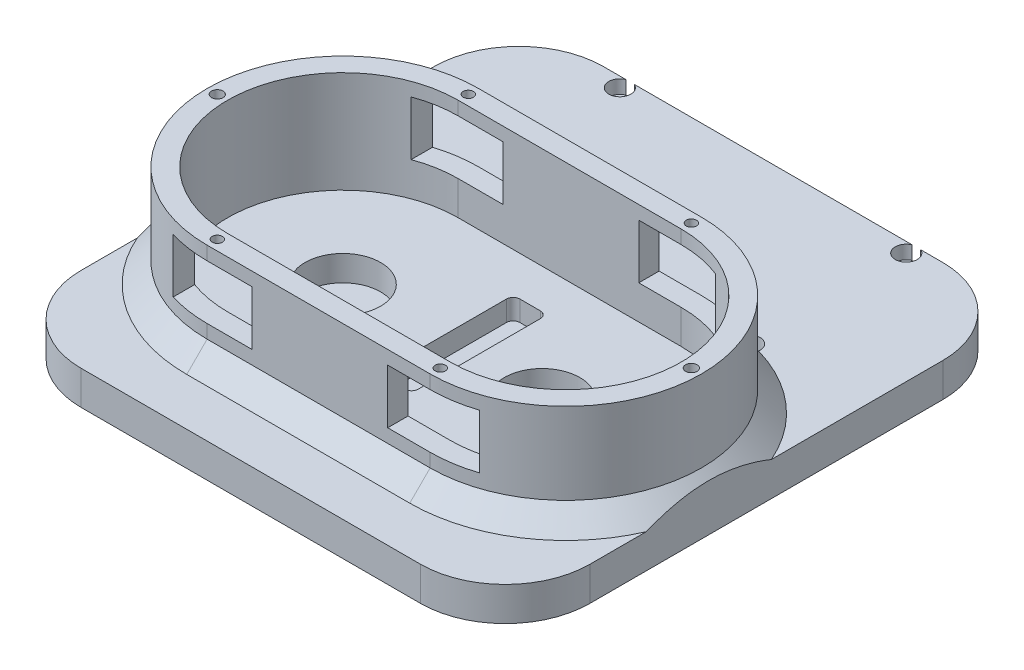
SolidWorks part; units mm, degrees
ref_plane "Front Plane" through (0, 0, 0) normal (0, 0, 1) x (1, 0, 0)
ref_plane "Top Plane" through (0, 0, 0) normal (0, 1, 0) x (1, 0, 0)
ref_plane "Right Plane" through (0, 0, 0) normal (1, 0, 0) x (0, 0, -1)
sketch "Sketch1" plane through (0, 0, 0) normal (0, 1, 0) x (1, 0, 0)
  line L0 (45, 40) -> (45, -40) construction
  line L8 (45, 40) -> (-20.73, 40)
  line L9 (45, -40) -> (-20.73, -40)
  arc A0 (45, -40) -> (45, 40) centre (45, 0) ccw
  circle A2 centre (38, 0) radius 28.73 construction
  arc A3 (-20.73, 40) -> (-20.73, -40) centre (-20.73, 0) ccw
  circle A4 centre (-20.73, 0) radius 30 construction
  point P0 (0, 0)
  dimension "D3" = 80
  dimension "D1" = 10
  dimension "D2" = 60
  dimension "D5" = 7
  dimension "D6" = 58.73
  dimension "D4" = 45
extrude "Boss-Extrude1" add sketch "Sketch1" along normal blind 10
sketch "Sketch2" plane through (0, 0, 0) normal (0, 1, 0) x (1, 0, 0)
  line L2 (-20.73, -40) -> (45, -40) construction
  line L3 (45, 40) -> (-20.73, 40) construction
  line L4 (45, 34) -> (-20.73, 34)
  line L5 (-20.73, -34) -> (45, -34)
  line L6 (45, 34) -> (-20.73, 34)
  line L7 (-20.73, -34) -> (45, -34)
  line L8 (-20.73, -40) -> (45, -40)
  line L9 (45, 40) -> (-20.73, 40)
  arc A2 (-20.73, 40) -> (-20.73, -40) centre (-20.73, 0) ccw construction
  arc A3 (45, -40) -> (45, 40) centre (45, 0) ccw construction
  arc A4 (45, -34) -> (45, 34) centre (45, 0) ccw
  arc A5 (-20.73, 34) -> (-20.73, -34) centre (-20.73, 0) ccw
  arc A6 (45, -34) -> (45, 34) centre (45, 0) ccw
  arc A7 (-20.73, 34) -> (-20.73, -34) centre (-20.73, 0) ccw
  arc A8 (-20.73, 40) -> (-20.73, -40) centre (-20.73, 0) ccw
  arc A9 (45, -40) -> (45, 40) centre (45, 0) ccw
  dimension "D1" = 6
extrude "Boss-Extrude2" add sketch "Sketch2" along normal blind 30 from surface starting at face at (12.135, 10, 0)
sketch "Sketch8" plane through (0, 0, 0) normal (0, 1, 0) x (1, 0, 0)
  line L0 (12.135, 40) -> (12.135, -40) construction
  line L1 (-20.73, 40) -> (45, 40) construction
  line L2 (45, -40) -> (-20.73, -40) construction
  line L3 (85, 0) -> (-60.73, 0) construction
  line L4 (-20.73, -40) -> (45, -40) construction
  line L5 (-62.865, -60) -> (87.135, -60)
  line L6 (-62.865, -60) -> (-62.865, 94)
  line L7 (-62.865, 94) -> (87.135, 94)
  line L8 (87.135, -60) -> (87.135, 94)
  arc A0 (45, -40) -> (45, 40) centre (45, 0) ccw construction
  arc A1 (-20.73, 40) -> (-20.73, -40) centre (-20.73, 0) ccw construction
  point P14 (12.135, 0)
  point P22 (12.135, 94)
  dimension "D1" = 54
  dimension "D2" = 150
  dimension "D3" = 20
extrude "Boss-Extrude3" add sketch "Sketch8" along normal blind 10
sketch "Sketch5" plane through (0, 0, 0) normal (0, 1, 0) x (1, 0, 0)
  arc A0 (-20.73, 40) -> (-20.73, -40) centre (-20.73, 0) ccw construction
  arc A1 (-20.73, 40) -> (-20.73, -40) centre (-20.73, 0) ccw construction
  arc A2 (45, -40) -> (45, 40) centre (45, 0) ccw construction
  arc A3 (45, -40) -> (45, 40) centre (45, 0) ccw construction
  circle A4 centre (-20.73, 0) radius 11.15
  circle A6 centre (38, 0) radius 11.15
  dimension "D1" = 7
  dimension "D2" = 22.3
extrude "Cut-Extrude2" cut sketch "Sketch5" against normal blind 7.5 from surface starting at face at (12.135, 10, 0)
sketch "Sketch7" plane through (0, 0, 0) normal (0, 0, 1) x (1, 0, 0)
  line L0 (45, 40) -> (45, 10) construction
  line L1 (-32.5, 20) -> (-7.5, 20)
  line L2 (-32.5, 20) -> (-32.5, 36)
  line L3 (-32.5, 36) -> (-7.5, 36)
  line L4 (-7.5, 20) -> (-7.5, 36)
  line L5 (-32.5, 20) -> (-7.5, 36) construction
  line L6 (-32.5, 36) -> (-7.5, 20) construction
  line L7 (32.5, 20) -> (57.5, 20)
  line L8 (32.5, 20) -> (32.5, 36)
  line L9 (32.5, 36) -> (57.5, 36)
  line L10 (57.5, 20) -> (57.5, 36)
  line L11 (32.5, 20) -> (57.5, 36) construction
  line L12 (32.5, 36) -> (57.5, 20) construction
  line L14 (-20, 44) -> (-20, 0) construction
  point P0 (-20, 28)
  point P5 (45, 28)
  dimension "D1" = 16
  dimension "D2" = 20
  dimension "D3" = 25
  dimension "D4" = 25
  dimension "D5" = 20
extrude "Cut-Extrude4" cut sketch "Sketch7" against normal through all both and the other way through all
chamfer "Chamfer1" distance 6 angle 45 4 edges at (12.135, 10, -40) (85, 10, 0) (-60.73, 10, 0) (12.135, 10, 40)
fillet "Fillet1" radius 25 4 edges at (-62.865, 5, -94) (-62.865, 5, 60) (87.135, 5, -94) (87.135, 5, 60)
sketch "Sketch9" plane through (0, 0, 0) normal (0, 1, 0) x (1, 0, 0)
  line L0 (79, 0) -> (85, 0) construction
  line L1 (-60.73, 0) -> (-54.73, 0) construction
  circle A0 centre (45, -37) radius 1.5
  circle A1 centre (-20.73, -37) radius 1.5
  circle A2 centre (45, 37) radius 1.5
  circle A3 centre (-20.73, 37) radius 1.5
  circle A4 centre (-57.73, 0) radius 1.7
  circle A5 centre (82, 0) radius 1.7
  arc A6 (45, -34) -> (45, 34) centre (45, 0) ccw construction
  arc A7 (45, -40) -> (45, 40) centre (45, 0) ccw construction
  arc A8 (-20.73, 40) -> (-20.73, -40) centre (-20.73, 0) ccw construction
  arc A9 (-20.73, 34) -> (-20.73, -34) centre (-20.73, 0) ccw construction
  dimension "D1" = 3
  dimension "D2" = 3.4
extrude "Cut-Extrude5" cut sketch "Sketch9" against normal up to surface (-36 mm away) from surface up to face at (45.032, 36, 36.4505) starting at face at (12.135, 40, 0)
sketch "Sketch10" plane through (-45.015, 10, -51.2) normal (0, 1, 0) x (1, 0, 0)
  line L0 (57.15, -11.2) -> (57.15, 55.5219) construction
  line L1 (24.285, -11.2) -> (90.015, -11.2) construction
  line L2 (107.15, 42.8) -> (7.15, 42.8) construction
  circle A4 centre (14.94, -6.52) radius 1.45
  circle A5 centre (99.36, -6.52) radius 1.45
  circle A6 centre (99.36, 39.8) radius 1.45
  circle A7 centre (14.94, 39.8) radius 1.45
  dimension "D1" = 2.9
  dimension "D3" = 46.32
  dimension "D2" = 84.42
  dimension "D4" = 3
extrude "Cut-Extrude6" cut sketch "Sketch10" against normal through all both and the other way through all
sketch "Sketch11" plane through (0, 0, 0) normal (0, 1, 0) x (1, 0, 0)
  circle A0 centre (-30.075, 44.68) radius 3.25
  circle A1 centre (-30.075, 91) radius 3.25
  circle A2 centre (54.345, 91) radius 3.25
  circle A3 centre (54.345, 44.68) radius 3.25
  dimension "D1" = 6.5
extrude "Cut-Extrude7" cut sketch "Sketch11" against normal blind 4 and the other way through all from surface starting at face at (-30.075, 10, -92.45)
sketch "Sketch12" plane through (0, 0, 0) normal (0, 1, 0) x (1, 0, 0)
  line L0 (15.135, 22.3477) -> (9.135, 22.3477) construction
  line L1 (15.135, 22.3477) -> (9.135, 22.3477)
  line L2 (17.135, -15.6523) -> (17.135, 20.3477) construction
  line L3 (17.135, -15.6523) -> (17.135, 20.3477)
  line L4 (7.135, 20.3477) -> (7.135, -15.6523)
  line L5 (9.135, -17.6523) -> (15.135, -17.6523)
  arc A0 (9.135, 22.3477) -> (7.135, 20.3477) centre (9.135, 20.3477) ccw construction
  arc A1 (17.135, 20.3477) -> (15.135, 22.3477) centre (15.135, 20.3477) ccw construction
  arc A2 (9.135, 22.3477) -> (7.135, 20.3477) centre (9.135, 20.3477) ccw
  arc A3 (17.135, 20.3477) -> (15.135, 22.3477) centre (15.135, 20.3477) ccw
  arc A4 (7.135, -15.6523) -> (9.135, -17.6523) centre (9.135, -15.6523) ccw
  arc A5 (7.135, -15.6523) -> (9.135, -17.6523) centre (9.135, -15.6523) ccw construction
  arc A10 (15.135, -17.6523) -> (17.135, -15.6523) centre (15.135, -15.6523) ccw
extrude "Cut-Extrude8" cut sketch "Sketch12" against normal blind 6 from surface starting at face at (-20.73, 10, 11.15)
